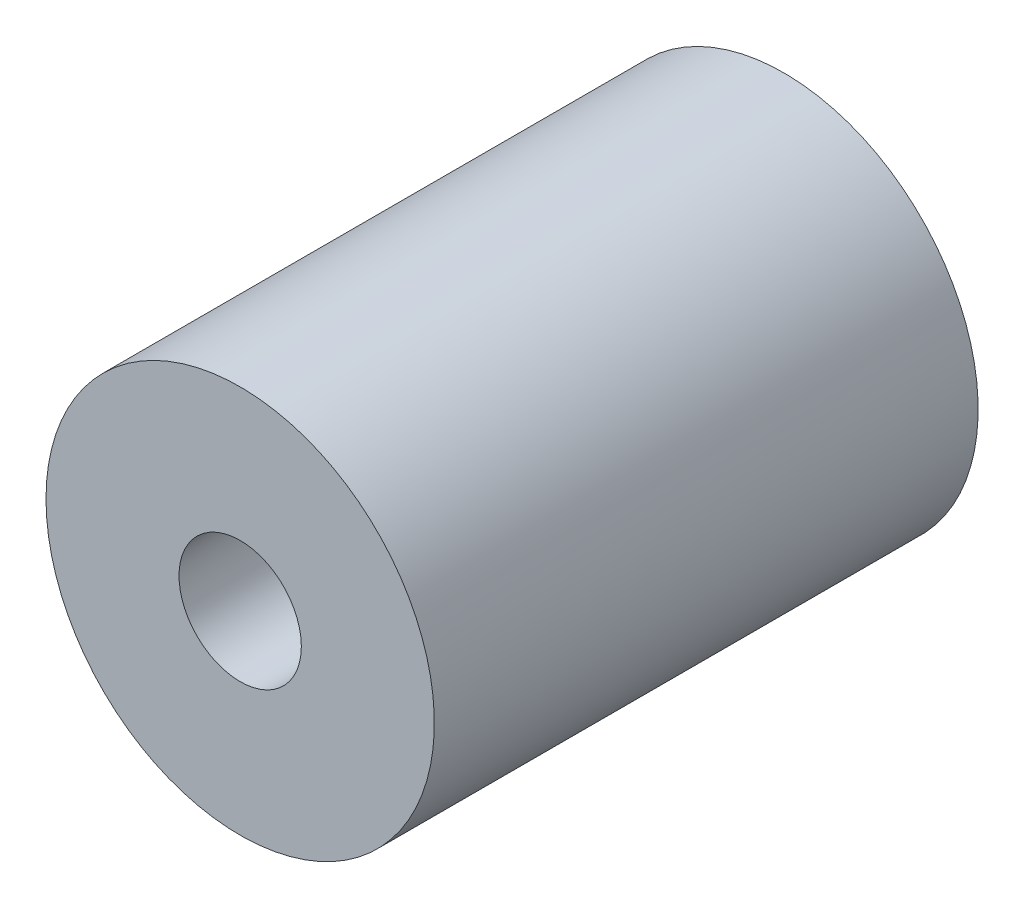
SolidWorks part; units mm, degrees
ref_plane "Front Plane" through (0, 0, 0) normal (0, 0, 1) x (1, 0, 0)
ref_plane "Top Plane" through (0, 0, 0) normal (0, 1, 0) x (1, 0, 0)
ref_plane "Right Plane" through (0, 0, 0) normal (1, 0, 0) x (0, 0, -1)
sketch "Sketch1" plane through (0, 0, 0) normal (0, 0, 1) x (1, 0, 0)
  circle A0 centre (0, 0) radius 9.525
  dimension "D1" = 19.05
extrude "Boss-Extrude1" add sketch "Sketch1" along a picked direction on the side of the normal blind 26.675 contours A0 | A0 region at (0, 0, 0)
sketch "Sketch2" plane through (0, 0, 26.675) normal (0, 0, 1) x (1, 0, 0)
  circle A0 centre (0, 0) radius 3
  dimension "D1" = 6
extrude "Cut-Extrude1" cut sketch "Sketch2" against normal through all
